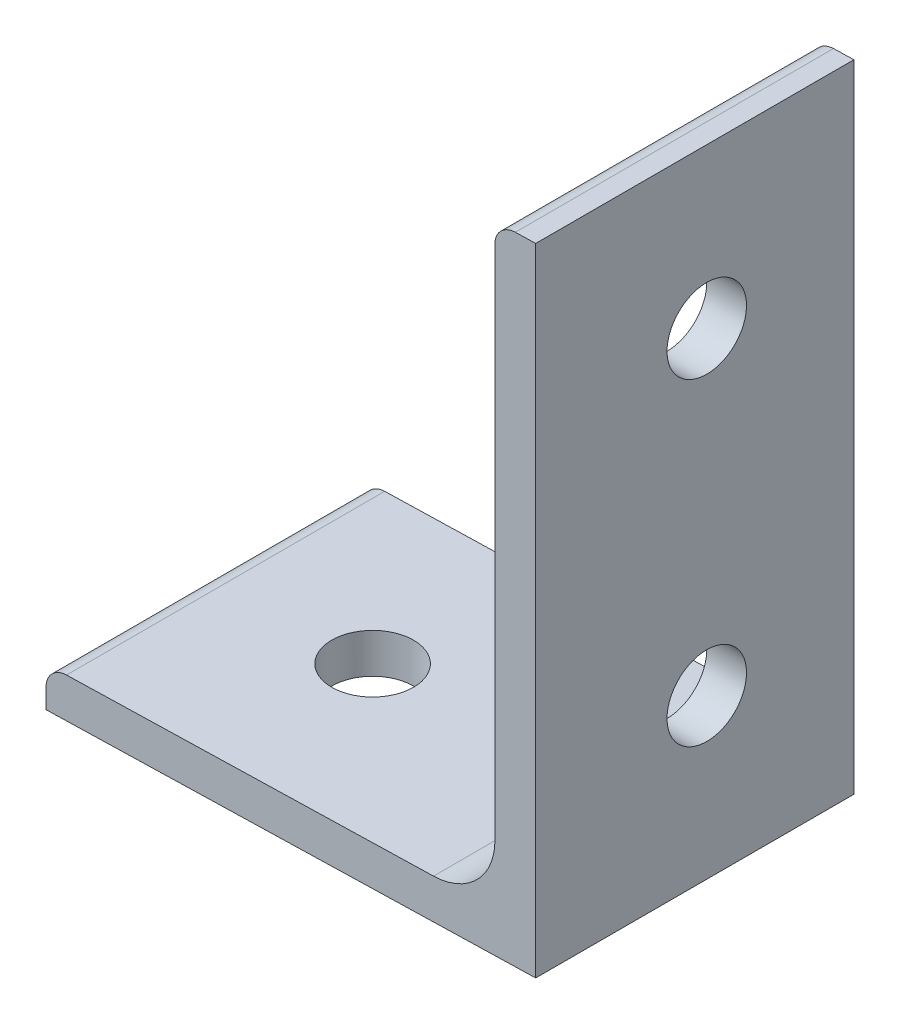
SolidWorks part; units mm, degrees
ref_plane "Front Plane" through (0, 0, 0) normal (0, 0, 1) x (1, 0, 0)
ref_plane "Top Plane" through (0, 0, 0) normal (0, 1, 0) x (1, 0, 0)
ref_plane "Right Plane" through (0, 0, 0) normal (1, 0, 0) x (0, 0, -1)
sketch "Sketch0" plane through (0, 0, 0) normal (0, 0, 1) x (1, 0, 0)
  line L0 (-19.05, -25.4) -> (19.05, -25.4)
  line L1 (19.05, -25.4) -> (19.05, 25.4)
  line L2 (19.05, 0) -> (0, 0) construction
  line L3 (0, 0) -> (0, -25.4) construction
  line L4 (15.875, -17.4498) -> (15.875, 25.4) construction
  line L5 (11.0998, -22.225) -> (-19.05, -22.225) construction
  arc A0 (15.875, -17.4498) -> (11.0998, -22.225) centre (11.0998, -17.4498) cw
  point P3 (14.4764, -20.8264)
  dimension "Inside Corner Radius" = 4.7752
  dimension "Outside Height" = 50.8
  dimension "Inside Height" = 47.625
  dimension "Inside Width" = 34.925
  dimension "Wall Thickness" = 3.175
  dimension "D1" = 3.175
  dimension "Outside Width" = 38.1
sketch "Sketch1" plane through (0, 0, 0) normal (1, 0, 0) x (0, 0, -1)
  line L0 (15.875, 0) -> (-15.875, 0)
  point P4 (0, 0)
  dimension "Length" = 31.75
sketch "Sketch2" plane through (0, 0, 0) normal (0, 0, 1) x (1, 0, 0)
  line L0 (-19.05, -25.4) -> (19.05, -25.4)
  line L1 (19.05, -25.4) -> (19.05, 25.4)
  line L2 (19.05, 25.4) -> (15.875, 25.4) construction
  line L3 (15.875, 23.8125) -> (15.875, -17.4498)
  line L4 (11.0998, -22.225) -> (-17.4625, -22.225)
  line L5 (-19.05, -25.4) -> (-19.05, -22.225) construction
  line L6 (17.4625, 25.4) -> (19.05, 25.4)
  line L7 (-19.05, -23.8125) -> (-19.05, -25.4)
  line L8 (19.05, 0) -> (0, 0) construction
  line L9 (0, 0) -> (0, -25.4) construction
  arc A0 (15.875, 23.8125) -> (17.4625, 25.4) centre (17.4625, 23.8125) cw
  arc A1 (-19.05, -23.8125) -> (-17.4625, -22.225) centre (-17.4625, -23.8125) cw
  arc A2 (15.875, -17.4498) -> (11.0998, -22.225) centre (11.0998, -17.4498) cw
  dimension "Inside Radius" = 4.7752
  dimension "Height" = 50.8
  dimension "Width" = 38.1
  dimension "Thickness" = 3.175
extrude "Boss-Extrude1" add sketch "Sketch2" along normal mid plane 31.75
sketch "Break Locations" plane through (0, 0, 0) normal (1, 0, 0) x (0, 0, -1)
  line L0 (35.941, 0) -> (-35.941, 0)
  line L1 (-15.875, -25.4) -> (-15.875, 25.4) construction
  line L2 (15.875, -25.4) -> (15.875, 25.4) construction
  point P0 (27.305, 0)
  point P1 (-27.305, 0)
  point P10 (0, 0)
  point P11 (-35.941, 0)
  point P13 (35.941, 0)
  dimension "D1" = 43.18
  dimension "D2" = 43.18
  dimension "D3" = 51.816
sketch "Sketch3" plane through (0, -25.4, 0) normal (0, -1, 0) x (1, 0, 0)
  line L0 (-19.05, -13.9268) -> (19.05, -14.9245)
  line L1 (19.05, 15.875) -> (19.05, -15.875) construction
  line L2 (19.05, -14.9245) -> (15.875, -14.8095) construction
  line L4 (-19.05, 11.4819) -> (19.05, 10.4842)
  line L5 (19.05, 10.4842) -> (19.05, -14.9245)
  line L6 (-19.05, -13.9268) -> (-19.05, 11.4819)
sketch "Sketch4" plane through (19.05, 0, 0) normal (1, 0, 0) x (0, 0, -1)
  line L0 (15.875, -25.4) -> (3.175, -25.4) construction
  line L1 (-15.875, -25.4) -> (15.875, -25.4) construction
  line L2 (3.175, -25.4) -> (3.175, -12.7) construction
  line L3 (3.175, -12.7) -> (3.175, 12.7) construction
  circle A0 centre (3.175, 12.7) radius 3.175
  circle A1 centre (3.175, -12.7) radius 3.175
  dimension "D1" = 12.7
  dimension "D2" = 12.7
  dimension "D3" = 25.4
extrude "Cut-Extrude1" cut sketch "Sketch4" against normal through all
extrude "Cut-Extrude2" cut sketch "Sketch3" against normal through all flip side to cut
hole_wizard "1/4 Clearance Hole1" positions "Sketch7" profile "Sketch8" hole size "1/4" standard "ANSI Inch" end condition through all
sketch "Sketch7" plane through (0, -25.4, 0) normal (0, -1, 0) x (-1, 0, 0)
  point P0 (6.0219, 1.5636)
sketch "Sketch8" plane through (-6.0219, -25.4, -1.5636) normal (1, 0, 0) x (0, 0, -1)
  line L0 (0, 0) -> (0, 50.8)
  line L1 (0, 50.8) -> (3.2639, 50.8)
  line L2 (3.2639, 50.8) -> (3.2639, 0)
  line L5 (3.2639, 0) -> (0, 0)
  line L11 (0, -6.35) -> (0, 107.95) construction
  dimension "Thru Hole Dia." = 6.5278
  dimension "Thru Hole Depth" = 50.8
sketch "Sketch9" plane through (15.875, 0, 0) normal (-1, 0, 0) x (0, 0, 1)
  circle A0 centre (-3.175, -12.7) radius 6.35
extrude "Cut-Extrude3" cut sketch "Sketch9" along normal blind 2.54
equation "\"D1@Break Locations\" = .85 * \"Height@Sketch2\""
equation "\"D2@Break Locations\"=\"D1@Break Locations\""
equation "\"Thickness@Sketch2\"=\"wall thickness@sketch0\""
equation "\"Height@Sketch2\"=\"outside height@sketch0\""
equation "\"Width@Sketch2\"=\"outside width@sketch0\""
equation "\"Inside Radius@Sketch2\"=\"inside corner radius@sketch0\""
equation "\"Length@Boss-Extrude1\"=\"length@sketch1\""
equation "\"D3@Break Locations\"=\"D2@Break Locations\"*1.2"
equation "\"D1@Sketch0\"=\"Wall Thickness@Sketch0\""
